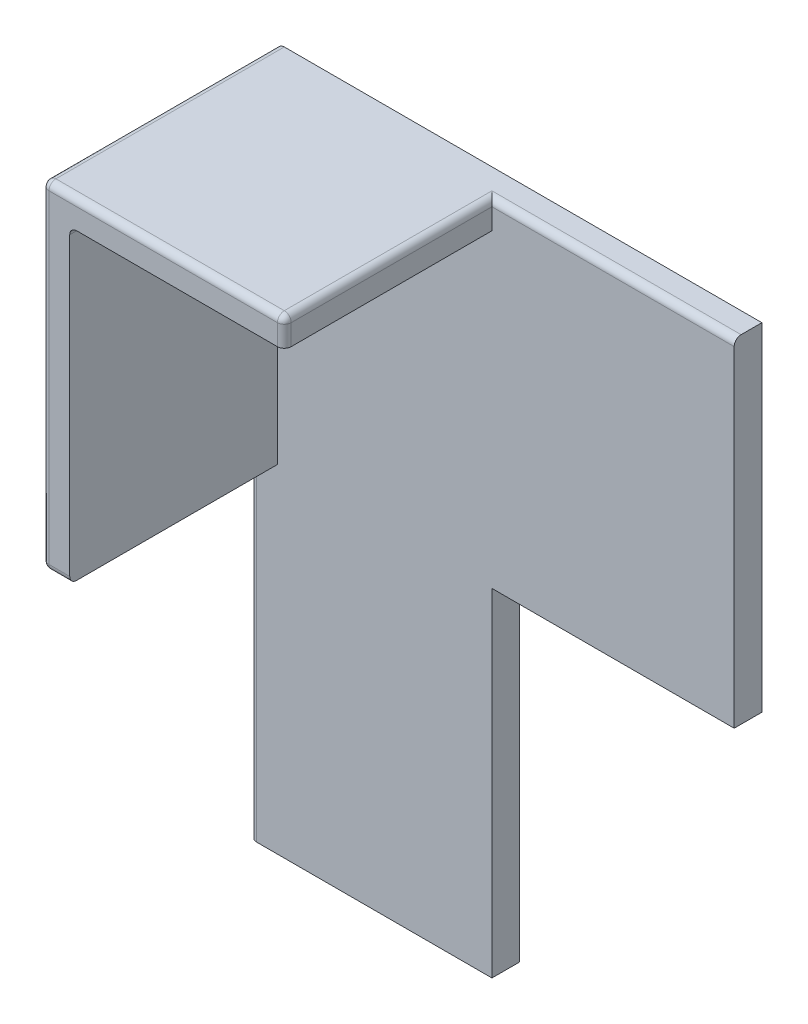
SolidWorks part; units mm, degrees
ref_plane "정면" through (0, 0, 0) normal (0, 0, 1) x (1, 0, 0)
ref_plane "윗면" through (0, 0, 0) normal (0, 1, 0) x (1, 0, 0)
ref_plane "우측면" through (0, 0, 0) normal (1, 0, 0) x (0, 0, -1)
sketch "스케치1" plane through (0, 0, 0) normal (0, 0, 1) x (1, 0, 0)
  line L1 (44.7488, 110.1527) -> (114.7488, 110.1527)
  line L2 (44.7488, 12.6527) -> (44.7488, -84.8473)
  line L3 (44.7488, -84.8473) -> (114.7488, -84.8473)
  line L4 (114.7488, 110.1527) -> (114.7488, -84.8473)
  line L5 (114.7488, 110.1527) -> (-25.2512, 110.1527)
  line L6 (114.7488, 110.1527) -> (114.7488, 12.6527)
  line L7 (44.7488, 12.6527) -> (-25.2512, 12.6527)
  line L8 (-25.2512, 110.1527) -> (-25.2512, 12.6527)
  dimension "D1" = 195
  dimension "D2" = 140
  dimension "D3" = 70
  dimension "D4" = 97.5
extrude "보스-돌출1" add sketch "스케치1" along normal blind 8 contours L5 L8 L7 L2 L3 L4 L1 region at (56.4155, 28.9027, 0)
sketch "스케치3" plane through (0, 0, 0) normal (0, 0, 1) x (1, 0, 0)
  line L0 (114.7488, 110.1527) -> (-25.2512, 110.1527) construction
  line L1 (104.2488, 103.1516) -> (105.9988, 100.1205)
  line L2 (105.9988, 100.1205) -> (109.4988, 100.1205)
  line L3 (109.4988, 100.1205) -> (111.2488, 103.1516)
  line L4 (111.2488, 103.1516) -> (109.4988, 106.1827)
  line L5 (109.4988, 106.1827) -> (105.9988, 106.1827)
  line L6 (105.9988, 106.1827) -> (104.2488, 103.1516)
  line L7 (114.7488, 110.1527) -> (114.7488, -84.8473) construction
  line L8 (44.7488, 12.6527) -> (-25.2512, 12.6527) construction
  line L9 (-21.7512, 82.1516) -> (-20.0012, 79.1205)
  line L10 (-20.0012, 79.1205) -> (-16.5012, 79.1205)
  line L11 (-16.5012, 79.1205) -> (-14.7512, 82.1516)
  line L12 (-14.7512, 82.1516) -> (-16.5012, 85.1827)
  line L13 (-16.5012, 85.1827) -> (-20.0012, 85.1827)
  line L14 (-20.0012, 85.1827) -> (-21.7512, 82.1516)
  line L15 (-21.7512, 21.6538) -> (-20.0012, 18.6227)
  line L16 (-20.0012, 18.6227) -> (-16.5012, 18.6227)
  line L17 (-16.5012, 18.6227) -> (-14.7512, 21.6538)
  line L18 (-14.7512, 21.6538) -> (-16.5012, 24.6848)
  line L19 (-16.5012, 24.6848) -> (-20.0012, 24.6848)
  line L20 (-20.0012, 24.6848) -> (-21.7512, 21.6538)
  line L21 (57.9988, 100.1205) -> (61.4988, 100.1205)
  line L22 (61.4988, 100.1205) -> (63.2488, 103.1516)
  line L23 (63.2488, 103.1516) -> (61.4988, 106.1827)
  line L24 (61.4988, 106.1827) -> (57.9988, 106.1827)
  line L25 (57.9988, 106.1827) -> (56.2488, 103.1516)
  line L26 (56.2488, 103.1516) -> (57.9988, 100.1205)
  line L27 (57.9988, 93.1805) -> (56.2488, 90.1494)
  line L28 (56.2488, 90.1494) -> (57.9988, 87.1183)
  line L29 (57.9988, 87.1183) -> (61.4988, 87.1183)
  line L30 (61.4988, 87.1183) -> (63.2488, 90.1494)
  line L31 (63.2488, 90.1494) -> (61.4988, 93.1805)
  line L32 (61.4988, 93.1805) -> (57.9988, 93.1805)
  line L33 (104.7488, -77.8462) -> (106.4988, -80.8773)
  line L34 (109.4988, 18.6205) -> (111.2488, 21.6516)
  line L35 (111.2488, 21.6516) -> (109.4988, 24.6827)
  line L36 (109.4988, 24.6827) -> (105.9988, 24.6827)
  line L37 (105.9988, 24.6827) -> (104.2488, 21.6516)
  line L38 (104.2488, 21.6516) -> (105.9988, 18.6205)
  line L39 (105.9988, 18.6205) -> (109.4988, 18.6205)
  line L40 (106.4988, -80.8773) -> (109.9988, -80.8773)
  line L41 (109.9988, -80.8773) -> (111.7488, -77.8462)
  line L42 (111.7488, -77.8462) -> (109.9988, -74.8152)
  line L43 (109.9988, -74.8152) -> (106.4988, -74.8152)
  line L44 (106.4988, -74.8152) -> (104.7488, -77.8462)
  line L46 (44.7488, -84.8473) -> (114.7488, -84.8473) construction
  line L47 (-25.2512, 110.1527) -> (-25.2512, 12.6527) construction
  circle A0 centre (107.7488, 103.1516) radius 3.0311 construction
  circle A1 centre (-18.2512, 82.1516) radius 3.5 construction
  circle A2 centre (-18.2512, 21.6538) radius 3.5 construction
  circle A3 centre (59.7488, 103.1516) radius 3.5 construction
  circle A4 centre (59.7488, 90.1494) radius 3.5 construction
  circle A5 centre (107.7488, 21.6516) radius 3.5 construction
  circle A6 centre (108.2488, -77.8462) radius 3.5 construction
  dimension "D5" = 7
  dimension "D8" = 7
  dimension "D11" = 7
  dimension "D14" = 7
  dimension "D17" = 7
  dimension "D20" = 7
  dimension "D1" = 7
  dimension "D2" = 3.97
  dimension "D3" = 3.5
  dimension "D4" = 3.5
  dimension "D6" = 24.97
  dimension "D7" = 3.5
  dimension "D9" = 5.97
  dimension "D10" = 3.5
  dimension "D12" = 3.97
  dimension "D13" = 81.5
  dimension "D15" = 6.94
  dimension "D16" = 81.5
  dimension "D18" = 3.5
  dimension "D19" = 85.47
  dimension "D21" = 3
  dimension "D22" = 3.97
extrude "컷-돌출2" cut sketch "스케치3" along normal blind 2 and the other way through all
sketch "스케치4" plane through (0, 0, 2) normal (0, 0, -1) x (-1, 0, 0)
  line L0 (-61.4988, 106.1827) -> (-57.9988, 106.1827) construction
  line L1 (-57.9988, 100.1205) -> (-61.4988, 100.1205) construction
  line L2 (-61.4988, 93.1805) -> (-57.9988, 93.1805) construction
  line L3 (-106.4988, -80.8773) -> (-109.9988, -80.8773) construction
  line L4 (-104.2488, 103.1516) -> (-105.9988, 100.1205) construction
  line L5 (-109.4988, 106.1827) -> (-105.9988, 106.1827) construction
  line L6 (-109.4988, 24.6827) -> (-105.9988, 24.6827) construction
  line L7 (-105.9988, 24.6827) -> (-104.2488, 21.6516) construction
  line L8 (-109.4988, 18.6205) -> (-111.2488, 21.6516) construction
  line L9 (-106.4988, -74.8152) -> (-104.7488, -77.8462) construction
  line L10 (20.0012, 79.1205) -> (16.5012, 79.1205) construction
  line L11 (20.0012, 85.1827) -> (21.7512, 82.1516) construction
  line L12 (16.5012, 79.1205) -> (14.7512, 82.1516) construction
  line L13 (21.7512, 21.6538) -> (20.0012, 18.6227) construction
  line L14 (20.0012, 24.6848) -> (21.7512, 21.6538) construction
  circle A0 centre (-59.7705, 103.1527) radius 2
  circle A1 centre (-59.7705, 90.1494) radius 2
  circle A2 centre (-107.7592, 103.1527) radius 2
  circle A3 centre (-108.2481, -77.8453) radius 2
  circle A4 centre (-107.7482, 21.6527) radius 2
  circle A5 centre (18.2525, 21.6538) radius 2
  circle A6 centre (18.2531, 82.1505) radius 2
  dimension "D1" = 4
  dimension "D4" = 4
  dimension "D7" = 4
  dimension "D9" = 4
  dimension "D13" = 4
  dimension "D16" = 4
  dimension "D20" = 4
  dimension "D2" = 3.03
  dimension "D3" = 3.0322
  dimension "D5" = 3.0311
  dimension "D6" = 6.0622
  dimension "D8" = 3.03
  dimension "D10" = 3.03
  dimension "D11" = 3.03
  dimension "D12" = 3.0322
  dimension "D14" = 3.03
  dimension "D15" = 3.032
  dimension "D17" = 3.03
  dimension "D18" = 3.03
  dimension "D19" = 3.0322
  dimension "D21" = 3.03
  dimension "D22" = 3.03
extrude "컷-돌출7" cut sketch "스케치4" against normal blind 5
sketch "스케치5" plane through (0, 0, 8) normal (0, 0, 1) x (1, 0, 0)
  line L0 (114.7488, 110.1527) -> (114.7488, -84.8473) construction
  line L1 (114.7488, 110.1527) -> (44.7488, 110.1527)
  line L2 (114.7488, 110.1527) -> (114.7488, 102.1527)
  line L3 (114.7488, 102.1527) -> (44.7488, 102.1527)
  line L4 (44.7488, 110.1527) -> (44.7488, 102.1527)
  line L5 (106.7488, 102.1527) -> (114.7488, 102.1527)
  line L6 (106.7488, 102.1527) -> (106.7488, 12.6527)
  line L7 (106.7488, 12.6527) -> (114.7488, 12.6527)
  line L8 (114.7488, 102.1527) -> (114.7488, 12.6527)
  line M8 (114.7488, -84.8473) -> (114.7488, 110.1527)
  dimension "D1" = 8
  dimension "D2" = 8
  dimension "D3" = 70
  dimension "D4" = 97.5
extrude "보스-돌출3" add sketch "스케치5" along normal blind 60 contours L6 L7 L3 M8 | L2 L1 L4 L3 region at (110.7488, 57.4027, 8)
fillet "필렛1" radius 2 7 edges at (114.7488, -36.0973, 8) (9.7488, 110.1527, 8) (44.7488, 110.1527, 38) (114.7488, 12.6527, 38) (79.7488, 110.1527, 68) (114.7488, 61.4027, 68) (114.7488, 110.1527, 34)
fillet "필렛2" radius 2 4 edges at (114.163, 13.2385, 67.4142) (45.3346, 109.5669, 67.4142) (109.7488, 12.6527, 68) (44.7488, 105.1527, 68)
fillet "필렛3" radius 2 1 edges at (106.7488, 102.1527, 38)
ref_plane "평면1" through (-35.2512, 0, 0) normal (-1, 0, 0) x (0, 0, 1)
mirror "대칭 복사1" about plane through (-35.2512, 0, 0) normal (-1, 0, 0) of bodies 107
delete or keep bodies "바디-삭제/보존 1" type delete bodies bodies 107
